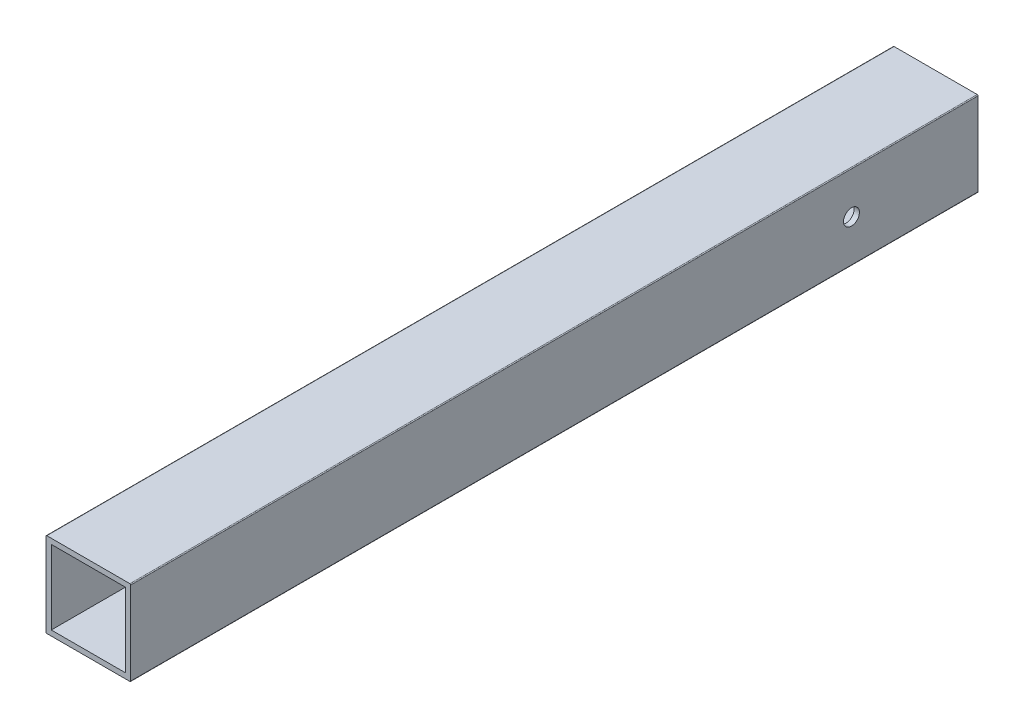
SolidWorks part; units mm, degrees
material "1060 Alloy"
ref_plane "Front Plane" through (0, 0, 0) normal (0, 0, 1) x (1, 0, 0)
ref_plane "Top Plane" through (0, 0, 0) normal (0, 1, 0) x (1, 0, 0)
ref_plane "Right Plane" through (0, 0, 0) normal (1, 0, 0) x (0, 0, -1)
ref_plane "Plane1" through (0, 0, 0) normal (0, 0, -1) x (-1, 0, 0)
sketch "Sketch1" plane through (0, 0, 0) normal (0, 0, -1) x (-1, 0, 0)
  line L4 (1.5875, -1.3335) -> (1.5875, 23.5585)
  line L5 (1.3335, 23.8125) -> (-23.5585, 23.8125)
  line L6 (-23.8125, 23.5585) -> (-23.8125, -1.3335)
  line L7 (-23.5585, -1.5875) -> (1.3335, -1.5875)
  line L9 (0, 22.225) -> (-22.225, 22.225)
  line L10 (0, 22.225) -> (0, 0)
  line L11 (0, 0) -> (-22.225, 0)
  line L12 (-22.225, 22.225) -> (-22.225, 0)
  line L13 (0, 22.225) -> (-22.225, 0) construction
  line L14 (0, 0) -> (-22.225, 22.225) construction
  arc A4 (1.3335, -1.5875) -> (1.5875, -1.3335) centre (1.3335, -1.3335) ccw
  arc A5 (1.5875, 23.5585) -> (1.3335, 23.8125) centre (1.3335, 23.5585) ccw
  arc A6 (-23.5585, 23.8125) -> (-23.8125, 23.5585) centre (-23.5585, 23.5585) ccw
  arc A7 (-23.8125, -1.3335) -> (-23.5585, -1.5875) centre (-23.5585, -1.3335) ccw
  point P24 (-11.1125, 11.1125)
  dimension "D1" = 25.4
  dimension "D2" = 25.4
  dimension "D3" = 1.5875
  dimension "D4" = 1.5875
  dimension "D5" = 1.5875
extrude "Boss-Extrude1" add sketch "Sketch1" against normal blind 254
sketch "Sketch2" plane through (-1.5875, 0, 0) normal (-1, 0, 0) x (0, 0, 1)
  line L0 (0, -1.3335) -> (0, 23.5585) construction
  line L1 (254, -1.3335) -> (0, -1.3335) construction
  line L2 (254, -1.3335) -> (254, 23.5585) construction
  circle A0 centre (12.6975, 11.3665) radius 1.5875
  circle A1 centre (241.3, 11.3665) radius 1.5875
  circle A2 centre (76.2, 11.3665) radius 6.35
  circle A3 centre (177.8, 11.3665) radius 6.35
  point P4 (0, 11.1125)
  dimension "D1" = 3.175
  dimension "D2" = 12.7
  dimension "D3" = 12.7
  dimension "D4" = 3.175
  dimension "D5" = 12.7
  dimension "D6" = 12.7
  dimension "D7" = 12.7
  dimension "D8" = 12.7
  dimension "D9" = 76.2
  dimension "D10" = 12.7
  dimension "D11" = 12.7
  dimension "D12" = 76.2
extrude "Cut-Extrude1" [suppressed] cut sketch "Sketch2" against normal through all
sketch "Sketch4" plane through (23.8125, 0, 0) normal (1, 0, 0) x (0, 0, -1)
  line L7 (-40.3145, 11.1125) -> (-35.552, 11.1125)
  line L8 (0, 23.5585) -> (0, -1.3335) construction
  line L9 (0, 11.1125) -> (-49.6378, 11.1125)
  circle A2 centre (-37.9333, 11.1125) radius 2.3812
  dimension "D1" = 4.7625
extrude "Cut-Extrude2" cut sketch "Sketch4" against normal through all contours A2
sketch "Sketch5" plane through (0, 23.8125, 0) normal (0, 1, 0) x (1, 0, 0)
  line L0 (11.1125, 0) -> (11.1125, -57.15) construction
  line L1 (-1.3335, 0) -> (23.5585, 0) construction
  circle A0 centre (11.1125, -57.15) radius 3.175
  dimension "D1" = 6.35
  dimension "D2" = 57.15
